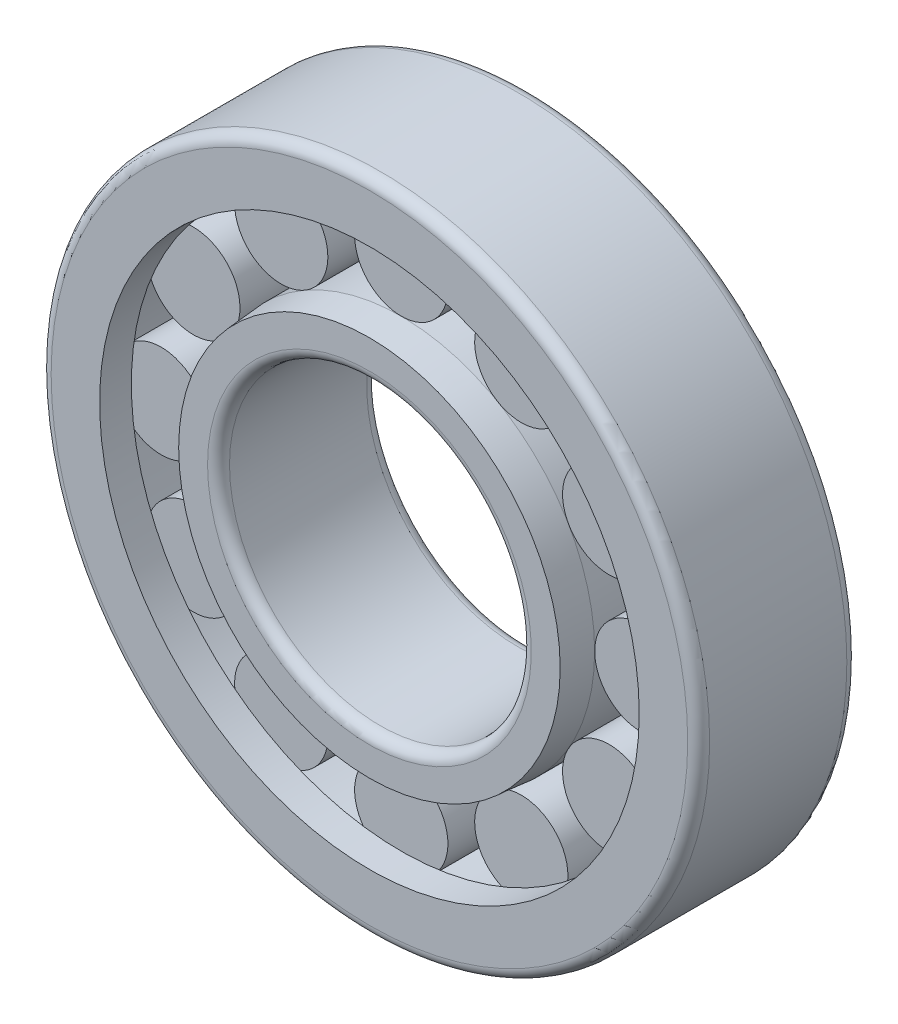
SolidWorks part; units mm, degrees
ref_plane "Front Plane" through (0, 0, 0) normal (0, 0, 1) x (1, 0, 0)
ref_plane "Top Plane" through (0, 0, 0) normal (0, 1, 0) x (1, 0, 0)
ref_plane "Right Plane" through (0, 0, 0) normal (1, 0, 0) x (0, 0, -1)
sketch "BaseSke" plane through (0, 0, 0) normal (1, 0, 0) x (0, 0, -1)
  line L0 (-47.2296, 0) -> (24.6132, 0) construction
  line L1 (-47.2296, 43.75) -> (24.6132, 43.75) construction
  line L2 (0, 129.5214) -> (0, -86.3012) construction
  line L3 (-8.7, 43.75) -> (-8.7, 52.25) construction
  line L4 (-14.5, 60) -> (14.5, 60) construction
  line L5 (-14.5, 27.5) -> (14.5, 27.5) construction
  line L6 (-8.7, 35.25) -> (8.7, 35.25)
  line L7 (-8.7, 35.25) -> (-8.7, 43.75)
  line L8 (-8.7, 43.75) -> (8.7, 43.75)
  line L9 (8.7, 35.25) -> (8.7, 43.75)
  line L10 (-8.7, 52.25) -> (8.7, 52.25) construction
  line L11 (8.7, 52.25) -> (8.7, 43.75) construction
  dimension "D2" = 17.4
revolve "Roller" add sketch "BaseSke" angle 360 about L8
sketch "OuterRaceSke" plane through (0, 0, 0) normal (1, 0, 0) x (0, 0, -1)
  line L0 (0, 0) -> (0, 87.5396) construction
  line L1 (-14.5, 60) -> (14.5, 60)
  line L2 (-14.5, 60) -> (-14.5, 49.1667)
  line L3 (-14.5, 49.1667) -> (-8.725, 49.1667)
  line L4 (14.5, 60) -> (14.5, 49.1667)
  line L5 (-50.3916, 0) -> (55.2197, 0) construction
  line L6 (-8.7, 52.25) -> (8.7, 52.25) construction
  line L7 (8.725, 49.1667) -> (14.5, 49.1667)
  line L9 (-8.725, 49.1667) -> (-8.725, 52.23)
  line L10 (-8.725, 52.23) -> (8.725, 52.23)
  line L11 (8.725, 49.1667) -> (8.725, 52.23)
  dimension "D2" = 98.3333
  dimension "D1" = 17.45
  dimension "D3" = 0.02
revolve "OuterRace" add sketch "OuterRaceSke" angle 360 about L5
sketch "InnerRaceSke" plane through (0, 0, 0) normal (1, 0, 0) x (0, 0, -1)
  line L0 (-70.8626, 0) -> (113.5527, 0) construction
  line L1 (0, 58.441) -> (0, -70.8113) construction
  line L2 (-14.5, 27.5) -> (14.5, 27.5)
  line L3 (-14.5, 27.5) -> (-14.5, 38.3333)
  line L4 (-8.725, 38.3333) -> (-8.725, 35.27)
  line L5 (-8.725, 38.3333) -> (-14.5, 38.3333)
  line L6 (0, 129.5214) -> (0, -86.3012) construction
  line L7 (-8.725, 35.27) -> (8.725, 35.27)
  line L9 (14.5, 27.5) -> (14.5, 38.3333)
  line L10 (8.725, 38.3333) -> (14.5, 38.3333)
  line L11 (8.725, 35.27) -> (8.725, 38.3333)
  line L13 (-8.7, 35.25) -> (8.7, 35.25) construction
  point P17 (0, 27.5)
  dimension "D1" = 17.45
  dimension "D2" = 0.02
  dimension "D3" = 76.6667
revolve "InnerRace" add sketch "InnerRaceSke" angle 360 about L0
fillet "Fillet1" radius 2 4 edges at (27.5, 0, 14.5) (60, 0, -14.5) (60, 0, 14.5) (27.5, 0, -14.5)
sketch "CutGrooveSke" plane through (0, 0, 0) normal (1, 0, 0) x (0, 0, -1)
  line L0 (-51.8407, 0) -> (83.8302, 0) construction
  line L1 (-7.25, -78.8) -> (-8.7, -78.8)
  line L2 (-7.25, -78.8) -> (-7.25, -58.8)
  line L3 (-7.25, -58.8) -> (-8.7, -58.8)
  line L4 (-8.7, -78.8) -> (-8.7, -58.8)
  dimension "D1" = 58.8
  dimension "D3" = 1.45
  dimension "D4" = 20
  dimension "D2" = 7.25
revolve "CutGroove" [suppressed] cut sketch "CutGrooveSke" angle 360 about L0
sketch "TaperSke" plane through (0, 0, 0) normal (1, 0, 0) x (0, 0, -1)
  line L0 (-14.5, 27.5) -> (14.5, 27.5)
  line L1 (14.5, 27.5) -> (14.5, 29.9167)
  line L2 (14.5, 29.9167) -> (-14.5, 27.5)
  line L7 (-41.2502, 0) -> (40.8606, 0) construction
revolve "Taper" [suppressed] cut sketch "TaperSke" angle 360 about L7
fillet "Fillet2" [suppressed] radius 2
sketch "NFSke" plane through (0, 0, 0) normal (1, 0, 0) x (0, 0, -1)
  line L0 (-54.6114, 0) -> (63.7655, 0) construction
  line L1 (14.5, 52.7352) -> (8.725, 52.23)
  line L2 (8.725, 52.23) -> (8.725, 49.1667)
  line L3 (8.725, 49.1667) -> (14.5, 49.1667)
  line L4 (14.5, 49.1667) -> (14.5, 52.7352)
  dimension "D1" = 5
revolve "NF" [suppressed] cut sketch "NFSke" angle 360 about L0
mirror "N" [suppressed] about plane through (0, 0, 0) normal (0, 0, 1)
sketch "NJSke" plane through (0, 0, 0) normal (1, 0, 0) x (0, 0, -1)
  line L0 (-35.6078, 0) -> (44.429, 0) construction
  line L1 (14.5, 38.3333) -> (8.725, 38.3333)
  line L2 (8.725, 38.3333) -> (8.725, 35.27)
  line L3 (8.725, 35.27) -> (14.5, 34.7648)
  line L4 (14.5, 34.7648) -> (14.5, 38.3333)
  dimension "D1" = 5
revolve "NJ" cut sketch "NJSke" angle 360 about L0
mirror "NU" about plane through (0, 0, 0) normal (0, 0, 1) of "NJ"
pattern_circular "CirPatternBall" count 12 over 360 about axis through (0, 0, 50.3916) along (0, 0, -1) of "Roller"
sketch "SimplifiedSke" plane through (0, 0, 0) normal (1, 0, 0) x (0, 0, -1)
  line L0 (37.5911, 0) -> (-37.5911, 0) construction
  line L1 (-13.1351, 43.75) -> (13.151, 43.75) construction
  line L2 (-8.7, 52.25) -> (8.7, 52.25)
  line L3 (-8.7, 52.25) -> (-8.7, 35.25)
  line L4 (-8.7, 35.25) -> (8.7, 35.25)
  line L5 (8.7, 52.25) -> (8.7, 35.25)
  line L6 (-47.2296, 43.75) -> (24.6132, 43.75) construction
revolve "Simplified" [suppressed] add sketch "SimplifiedSke" angle 360 about L0
equation "\"D2@BaseSke\" = \"Bearing_Thickness@BaseSke\"*0.6"
equation "\"D1@OuterRaceSke\" = \"Bearing_Thickness@BaseSke\"*0.6+0.05"
equation "\"D2@OuterRaceSke\" =\"Bearing_Outside_Diameter@BaseSke\" -  ( \"Bearing_Outside_Diameter@BaseSke\" - \"Bearing_Inside_Diameter@BaseSke\"  )/ 3 "
equation "\"D1@InnerRaceSke\" = \"Bearing_Thickness@BaseSke\"*0.6+0.05"
equation "\"D3@InnerRaceSke\" = \"Bearing_Inside_Diameter@BaseSke\" +  ( \"Bearing_Outside_Diameter@BaseSke\" - \"Bearing_Inside_Diameter@BaseSke\" ) / 3 "
equation "\"D1@CirPatternBall\" =  int(  ( \"Bearing_Outside_Diameter@BaseSke\" + \"Bearing_Inside_Diameter@BaseSke\" )  / 2 *  pi  /  ( \"Bearing_Outside_Diameter@BaseSke\" - \"Bearing_Inside_Diameter@BaseSke\" ) * 3 ) "
equation "\"D1@CutGrooveSke\" = \"Bearing_Outside_Diameter@BaseSke\" * 0.49"
equation "\"D2@CutGrooveSke\" = \"Bearing_Thickness@BaseSke\" *0.25"
equation "\"D3@CutGrooveSke\" = \"Bearing_Thickness@BaseSke\"/20"
equation "\"Taper@TaperSke\" = \"Bearing_Thickness@BaseSke\"/12"
equation "\"D1@Fillet2\" = \"Fillet_radius@Fillet1\""
